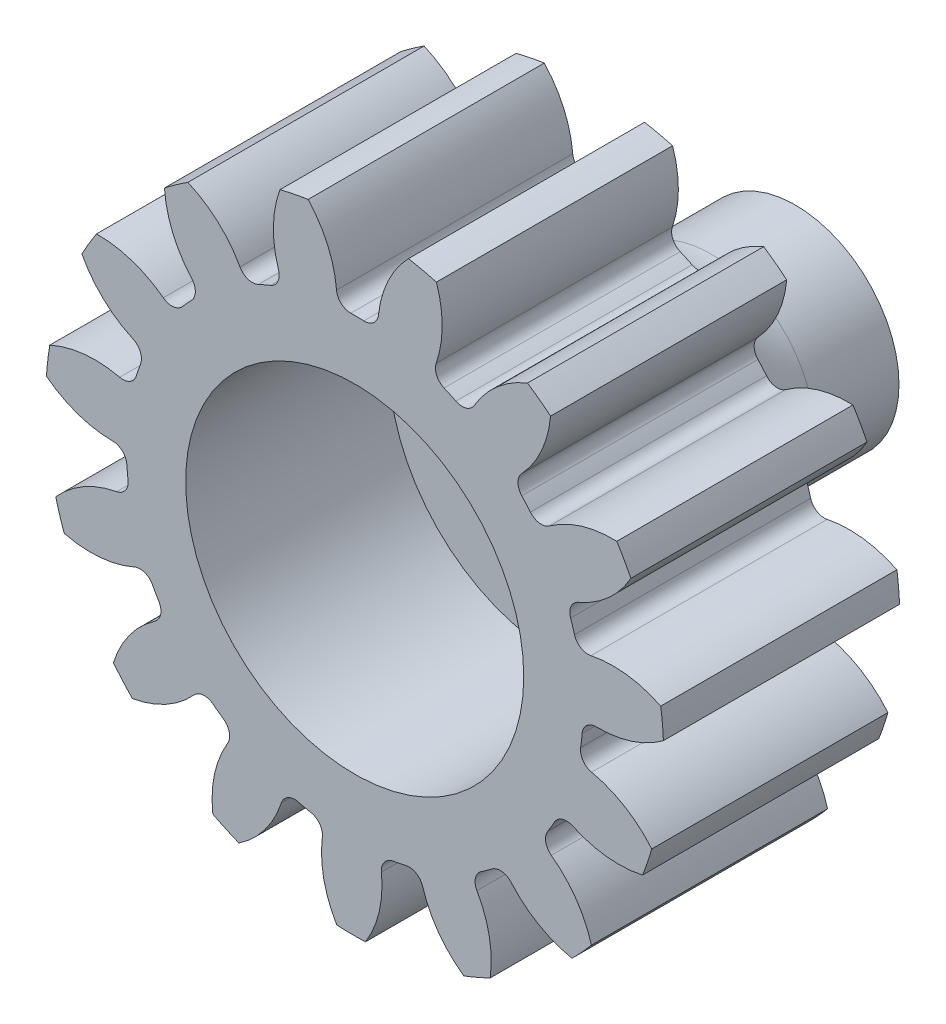
SolidWorks part; units mm, degrees
material "ABS"
ref_plane "Front" through (0, 0, 0) normal (0, 0, 1) x (1, 0, 0)
ref_plane "Top" through (0, 0, 0) normal (0, 1, 0) x (1, 0, 0)
ref_plane "Right" through (0, 0, 0) normal (1, 0, 0) x (0, 0, -1)
sketch "Sketch3" plane through (0, 0, 0) normal (0, 0, 1) x (1, 0, 0)
  circle A0 centre (0, 0) radius 21.59
  dimension "od" = 43.18
extrude "gearBody" add sketch "Sketch3" along normal blind 11
sketch "Sketch2" plane through (0, 0, 0) normal (0, 0, 1) x (1, 0, 0)
  line L0 (0, 0) -> (17.0393, 7.0579) construction
  line L1 (22.0105, -8.0941) -> (0, 0) construction
  line L2 (0, 0) -> (36.3143, 0) construction
  line L3 (19.0486, -0.229) -> (18.5878, -4.1711) construction
  line L5 (18.8182, -2.2) -> (0, 0) construction
  line L7 (0, 0) -> (18.4432, 0) construction
  arc A0 (18.4395, -0.3701) -> (18.0276, -3.8932) centre (0, 0) ccw construction
  arc A1 (21.5666, 1.0048) -> (20.7532, -5.9524) centre (0, 0) ccw construction
  arc A2 (19.0486, -0.229) -> (18.5878, -4.1711) centre (0, 0) ccw construction
  arc A3 (15.7838, -2.3046) -> (15.8898, -1.3984) centre (0, 0) ccw
  arc A4 (22.0105, -8.0941) -> (16.5506, -3.4102) centre (14.9518, -10.798) ccw
  arc A5 (22.0105, -8.0941) -> (23.2839, 2.7987) centre (0, 0) ccw
  arc A6 (23.2839, 2.7987) -> (16.8909, -0.4995) centre (17.0393, 7.0579) cw
  arc A7 (15.8898, -1.3984) -> (16.8909, -0.4995) centre (16.8715, -1.4848) cw
  arc A8 (16.5506, -3.4102) -> (15.7838, -2.3046) centre (16.759, -2.4469) cw
  point P6 (23.2839, 2.7987)
  point P22 (22.0105, -8.0941)
  dimension "baseDia" = 36.8864
  dimension "od" = 43.18
  dimension "pd" = 38.1
  dimension "rd" = 31.9024
  dimension "rFillet" = 0.9855
  dimension "pointX" = 23.2839
  dimension "pointY" = 2.7987
  dimension "CTT" = 3.9421
  dimension "flankCenterAngle" = 22.5
extrude "toothCut" cut sketch "Sketch2" along normal through all
pattern_circular "CirPattern1" count 15 over 360 about axis through (0, 0, 11) along (0, 0, -1) of "toothCut"
scale "Scale1" scale about centroid uniform scaling no x scale factor 0.666667 y scale factor 0.666667 z scale factor 1
sketch "hub1Dia" plane through (0, 0, 0) normal (0, 0, -1) x (-1, 0, 0)
  circle A0 centre (0, 0) radius 12.7
  dimension "hub1Dia" = 25.4
sketch "hub2Dia" plane through (0, 0, 11) normal (0, 0, 1) x (1, 0, 0)
  circle A0 centre (0, 0) radius 12.7
  dimension "hub2dia" = 25.4
sketch "boreDia" plane through (0, 0, 0) normal (0, 0, 1) x (1, 0, 0)
  circle A0 centre (0, 0) radius 7.874
  dimension "boreDia" = 15.748
extrude "bore" cut sketch "boreDia" against normal mid plane 25400
sketch "Sketch4" plane through (0, 0, 0) normal (1, 0, 0) x (0, 0, -1)
  line L0 (9.525, 0) -> (-1.524, 0)
  line L1 (-1.524, 0) -> (-1.524, 7.874)
  line L2 (-1.524, 7.874) -> (0, 7.874)
  line L3 (0, 8.1454) -> (0, 11.133) construction
  line L4 (0, 7.874) -> (0, 10.414)
  line L7 (5.588, 4.826) -> (9.525, 4.826)
  line L8 (9.525, 4.826) -> (9.525, 0)
  line L9 (0, 0) -> (18.4907, 0) construction
  arc A0 (0, 10.414) -> (5.588, 4.826) centre (5.588, 10.414) ccw
  dimension "D2" = 5.588
  dimension "D1" = 15.748
  dimension "D3" = 1.524
  dimension "D5" = 9.652
  dimension "D6" = 9.525
revolve "Revolve1" add sketch "Sketch4" angle 360 about L9
sketch "Sketch5" plane through (0, 0, -9.525) normal (0, 0, -1) x (-1, 0, 0)
  circle A0 centre (0, 0) radius 2.65
  dimension "D1" = 5.3
extrude "Cut-Extrude1" cut sketch "Sketch5" against normal blind 3.746
sketch "Sketch6" plane through (0, 0, -9.525) normal (0, 0, -1) x (-1, 0, 0)
  line L0 (0, 0) -> (0, 3.8857) construction
  line L1 (0.06, 3.0494) -> (0.23, 2.64)
  line L2 (-0.06, 3.0494) -> (-0.23, 2.64)
  circle A0 centre (0, 0) radius 2.65 construction
  arc A1 (0.23, 2.64) -> (-0.23, 2.64) centre (0, 0) ccw
  arc A2 (0.06, 3.0494) -> (-0.06, 3.0494) centre (0, 0) ccw
  dimension "D1" = 6.1
  dimension "D2" = 0.06
  dimension "D3" = 0.23
extrude "Cut-Extrude4" cut sketch "Sketch6" against normal blind 3.746
pattern_circular "CirPattern2" count 25 over 360 about axis through (0, 0, -5.779) along (0, 0, -1) of "Cut-Extrude4"
equation "\"Motor_OD\" = 54.4mm"
equation "\"Motor_Length\" = 401mm"
equation "\"Aft_Section_Length\" = 32in"
equation "\"Mid_Coupler_Length\" = 12in"
equation "\"AB_Coupler_OD_Length\"= 1in"
equation "\"AB_Coupling_Section_Length\"= 0.375in"
equation "\"AB_Coupler_Length\"= \"AB_Coupler_OD_Length\" + \"AB_Coupling_Section_Length\" * 2"
equation "\"Cutout_Angle\" = 60"
equation "\"AB_Paddle_Height\" = 0.375in"
equation "\"AB_Coupler_Num_Screws\"= 4"
equation "\"Num_Cutouts\" = 4"
equation "\"AB_Coupler_OD\"= 4.024in"
equation "\"AB_Coupler_ID\"= 3.7in"
equation "\"AB_Coupler_Surface_Diameter\"= 3.899in"
equation "\"AB_Coupling_Screw_Diameter\"= 4.5mm"
equation "\"AB_Central_Bushing_Length\" = 0.75in"
equation "\"Lead_Screw_Dist\" = 2in"
equation "\"Lead_Screw_Diam\" = 0.375in"
equation "\"Lead_Screw_Length\" = \"Mid_Coupler_Length\" + 2*0.375in + 2*0.5in"
equation "\"Paddle_Pin_Offset\" = 0.25in"
equation "\"Paddle_Pin_Radius\" = 2.25*2/3in"
equation "\"Paddle_Gear_OD\" = 3.2in"
equation "\"Fwd_BKHD_From_Top\" = 18in"
equation "\"Body_Tube_OD\"= 4.024in"
equation "\"Body_Tube_ID\"= 3.90in"
equation "\"Coupler_OD\" = 3.899in"
equation "\"Coupler_ID\" = 3.755in"
equation "\"Fwd_Section_Length\" = 20in"
equation "\"Mid_Section_Length\" = 4in"
equation "\"Aft_Upper_Tube_Length\" = 10in"
equation "\"Aft_Lower_Tube_Length\" = 18in"
equation "\"Nosecone_Coupler_Length\" = 5in"
equation "\"Avionics_Bulkhead_Thickness\" = 0.25in"
equation "\"Avionics_Bulkhead_Lip\" = 0.125in"
equation "\"Avionics_Board_Length\" = \"Mid_Coupler_Length\" - 2*\"Avionics_Bulkhead_Lip\""
equation "\"Lead_Screw_Hole_Diam\" = 0.386in"
equation "\"Centering_Ring_Cutout_Dia\"= 1in"
equation "\"Fin_Thickness\" = 0.118in"
equation "\"Airbrakes_Wire_Hole_Dist\" = 1.1*2/3in"
equation "\"Airbrakes_Wire_Hole_Dia\" = 0.25in"
equation "\"Drive_Gear_OD\" = 1.7*2/3in"
equation "\"DB9_Hole_Dist\" = 25mm"
equation "\"DB9_Relief_Width\" = 0.47in"
equation "\"DB9_Relief_Hole_Offset\" = 0.09in"
equation "\"Servo_Gear_Offset\" = 0.5in"
equation "\"Mounting_Bracket_Centerhole_DIA\" = 0.4in"
equation "\"Drive_Gear_Shaft_DIA\" = \"Mounting_Bracket_Centerhole_DIA\" - 0.02in"
equation "\"Drive_Gear_Fillet\" = 0.22in"
equation "\"Drive_Gear_ID\" = 0.62in"
equation "\"M3_Thread_Clearance\" = 3.8mm"
equation "\"M3_Screw_Head_Diam\" = 6.5mm"
equation "\"Screw_Angle\" = 12.5deg"
equation "\"M3_Insert_OD\" = 4.1mm"
equation "\"M4_Insert_OD\" = 5.5mm"
equation "\"Mounting_Hole_Dist\" = 0.15in"
equation "\"Cam_Slot_Length\" = 7mm"
equation "\"Cam_Slot_Width\" = 10mm"
equation "\"D2@Sketch4\"=\"Drive_Gear_Fillet\""
equation "\"D5@Sketch4\"=\"Drive_Gear_Shaft_DIA\""
equation "\"D1@Sketch4\"=\"Drive_Gear_ID\""
equation "\"Drive_Gear_Offset\" = 0.01in"
